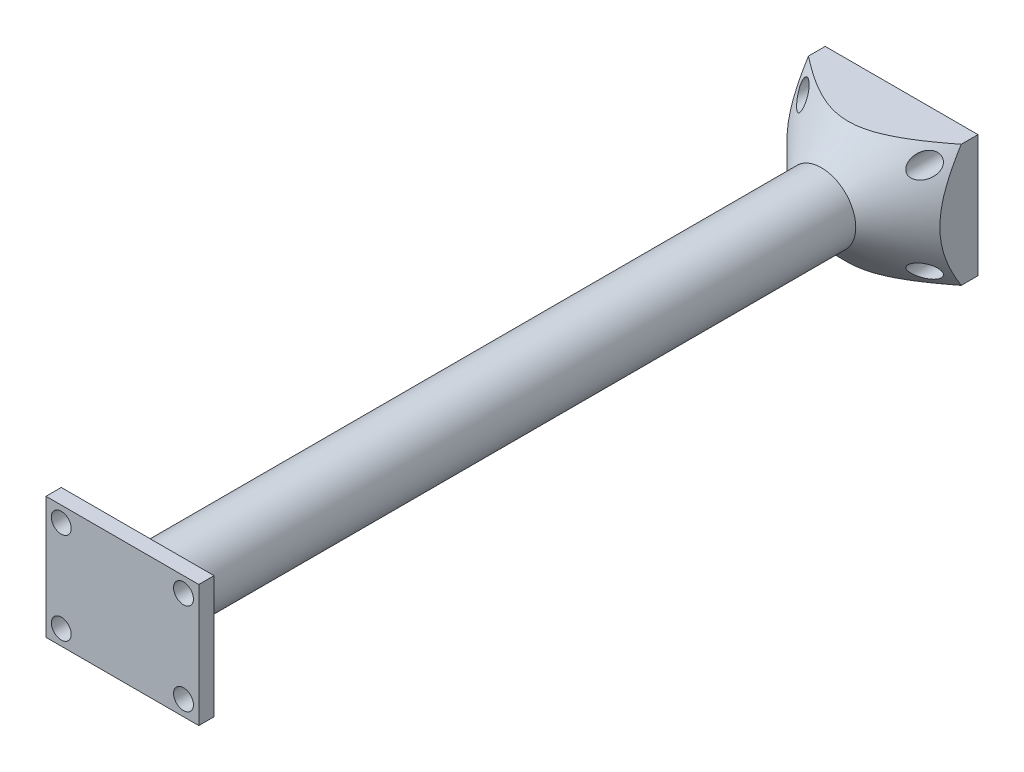
SolidWorks part; units mm, degrees
material "PMMA"
ref_plane "前视基准面" through (0, 0, 0) normal (0, 0, 1) x (1, 0, 0)
ref_plane "上视基准面" through (0, 0, 0) normal (0, 1, 0) x (1, 0, 0)
ref_plane "右视基准面" through (0, 0, 0) normal (1, 0, 0) x (0, 0, -1)
other "Configuration Table"
sketch "Sketch1" plane through (0, 0, 0) normal (0, 0, 1) x (1, 0, 0)
  line L5 (-8, 6) -> (8, 6)
  line L6 (-8, 6) -> (-8, -6)
  line L7 (-8, -6) -> (8, -6)
  line L8 (8, 6) -> (8, -6)
  line L9 (0, -6) -> (0, 6) construction
  line L10 (-8, 0) -> (8, 0) construction
  line L11 (-10, 8) -> (10, 8)
  line L12 (-10, 8) -> (-10, -8)
  line L13 (-10, -8) -> (10, -8)
  line L14 (10, 8) -> (10, -8)
  line L15 (0, -8) -> (0, 8) construction
  line L16 (-10, 0) -> (10, 0) construction
  circle A6 centre (0, 0) radius 4.5
  circle A7 centre (-8, 6) radius 1.3
  circle A8 centre (8, 6) radius 1.3
  circle A9 centre (8, -6) radius 1.3
  circle A10 centre (-8, -6) radius 1.3
  dimension "D1" = 12
  dimension "D2" = 16
  dimension "D3" = 16
  dimension "D4" = 20
extrude "Boss-Extrude1" add sketch "Sketch1" along normal blind 2 contours A6 | L14 L11 L12 L13 A10 L6 A7 L5 A8 L8 A9 L7 region at (0, 5.8, 0) region at (0, 7.7439, 0)
extrude "Boss-Extrude2" add sketch "Sketch1<3>" along normal blind 100 contours A6 region at (0, 0, 0)
sketch "Sketch1<3>" plane through (0, 0, 0) normal (0, 0, 1) x (1, 0, 0) same geometry as "Sketch1"
sketch "Sketch2" plane through (0, 0, 100) normal (0, 0, 1) x (1, 0, 0)
  line L1 (-10, 8) -> (10, 8)
  line L2 (-10, 8) -> (-10, -8)
  line L3 (-10, -8) -> (10, -8)
  line L4 (10, 8) -> (10, -8)
  line L5 (0, -8) -> (0, 8) construction
  line L6 (-10, 0) -> (10, 0) construction
  line L7 (-8, 6) -> (8, 6)
  line L8 (-8, 6) -> (-8, -6)
  line L9 (-8, -6) -> (8, -6)
  line L10 (8, 6) -> (8, -6)
  line L11 (0, -6) -> (0, 6) construction
  line L12 (-8, 0) -> (8, 0) construction
  circle A0 centre (-8, 6) radius 1.3
  circle A1 centre (8, 6) radius 1.3
  circle A2 centre (8, -6) radius 1.3
  circle A3 centre (-8, -6) radius 1.3
  point P0 (0, 0)
  point P4 (0, 0)
  circle M1 centre (0, 0) radius 4.5
  dimension "D1" = 16
  dimension "D2" = 20
  dimension "D3" = 12
  dimension "D4" = 16
extrude "Boss-Extrude3" add sketch "Sketch2" along normal blind 2 contours L4 L1 L2 L3 A3 L8 A0 L7 A1 L10 A2 L9 | A3 L9 A2 L10 A1 L7 A0 L8 M1 | M1 region at (0, 7.7439, 100) region at (0, 5.8, 100) region at (0, 0, 100)
chamfer "Chamfer1" distance 8.5 angle 45 1 edges at (4.5, 0, 2)
chamfer "Chamfer2" distance 3 angle 45 1 edges at (4.5, 0, 100)
